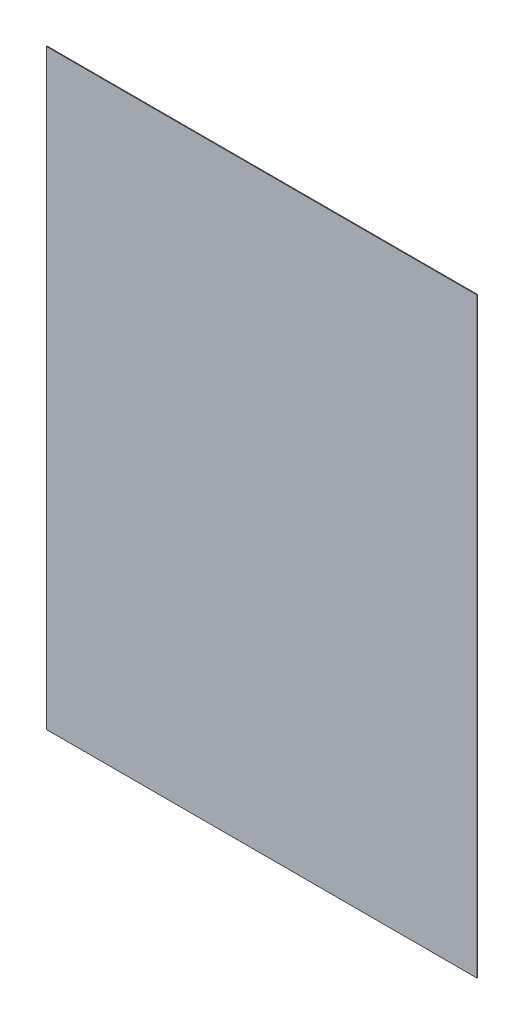
SolidWorks part; units mm, degrees
ref_plane "Front Plane" through (0, 0, 0) normal (0, 0, 1) x (1, 0, 0)
ref_plane "Top Plane" through (0, 0, 0) normal (0, 1, 0) x (1, 0, 0)
ref_plane "Right Plane" through (0, 0, 0) normal (1, 0, 0) x (0, 0, -1)
sketch "Sketch1" plane through (0, 0, 0) normal (0, 0, 1) x (1, 0, 0)
  line L1 (0, 0) -> (1215, 0)
  line L2 (0, 0) -> (0, 1670)
  line L3 (0, 1670) -> (1215, 1670)
  line L4 (1215, 0) -> (1215, 1670)
  dimension "D1" = 1215
  dimension "D2" = 1670
extrude "Boss-Extrude1" add sketch "Sketch1" along normal blind 2
